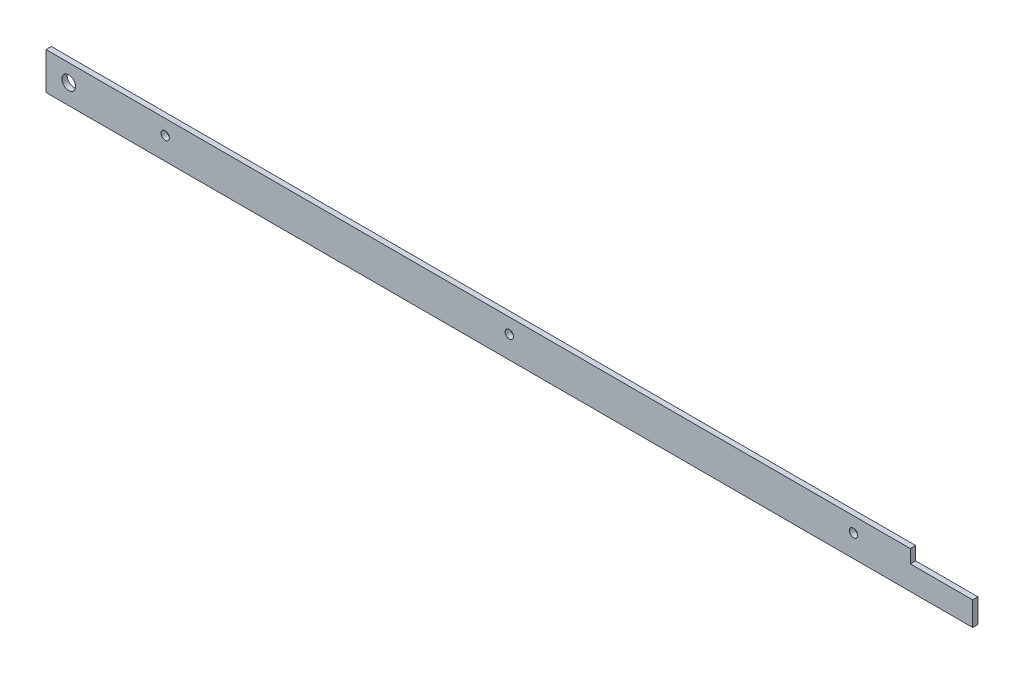
SolidWorks part; units mm, degrees
ref_plane "Front Plane" through (0, 0, 0) normal (0, 0, 1) x (1, 0, 0)
ref_plane "Top Plane" through (0, 0, 0) normal (0, 1, 0) x (1, 0, 0)
ref_plane "Right Plane" through (0, 0, 0) normal (1, 0, 0) x (0, 0, -1)
sketch "Sketch1" plane through (0, 0, 0) normal (0, 0, 1) x (1, 0, 0)
  line L0 (515.86, 17.392) -> (0, 17.392) construction
  line L5 (515.86, 41.507) -> (515.86, -0.373) construction
  line L6 (553.1, 9.447) -> (515.86, 9.447) construction
  line L9 (0, -4.833) -> (553.1, -4.833)
  line L10 (553.1, 9.447) -> (553.1, -4.833)
  line L11 (0, -4.833) -> (0, 45.967) construction
  line L12 (516.014, 17.392) -> (0, 17.392)
  line L13 (0, -4.833) -> (0, 17.392)
  line L14 (516.014, 17.392) -> (515.86, 17.392)
  line L15 (515.86, 9.447) -> (515.86, 17.392)
  line L16 (0, 20.567) -> (553.1, 20.567) construction
  line L17 (515.86, 9.447) -> (553.1, 9.447)
  line L19 (0, 20.567) -> (457.2, 20.567) construction
  circle A0 centre (71.12, 8.5095) radius 2.4892 construction
  circle A1 centre (13.54, 34.107) radius 13.54 construction
  circle A2 centre (13.54, 34.107) radius 4.0635 construction
  circle A6 centre (71.12, 8.5095) radius 2.4892
  circle A7 centre (276.55, 8.5095) radius 2.4892
  circle A8 centre (481.98, 8.5095) radius 2.4892
  circle A9 centre (13.54, 7.027) radius 4.0635
  dimension "D1" = 8.127
extrude "Boss-Extrude1" add sketch "Sketch1" along normal blind 3.175 contours L17 L15 L14 L12 L13 L9 L10 A8 A7 A6 region at (271.2776, 6.0875, 0)
